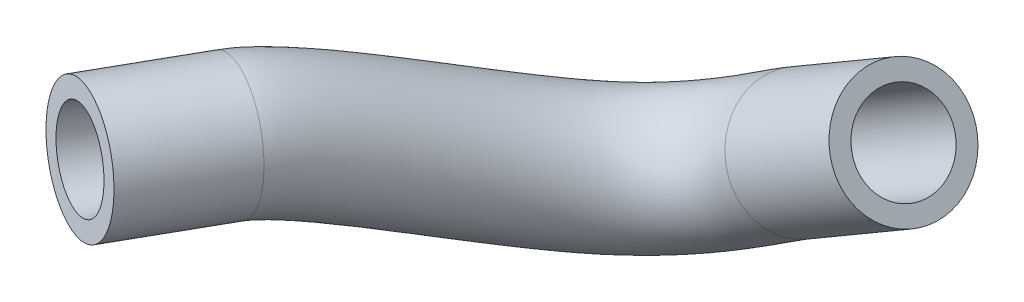
SolidWorks part; units mm, degrees
material "Silicon Rubber"
ref_plane "X-Y Datum" through (0, 0, 0) normal (0, 0, 1) x (1, 0, 0)
ref_plane "X-Z Datum" through (0, 0, 0) normal (0, 1, 0) x (1, 0, 0)
ref_plane "Y-Z Datum" through (0, 0, 0) normal (1, 0, 0) x (0, 0, -1)
sketch3d "3DSketch1"
  line L0 (-8.4082, 71.6879, 109.9525) -> (1.2518, 69.4078, 86.572)
  line L1 (58.6408, 60.7321, 18.5097) -> (85.1939, 77.7553, 22.1439)
  line L2 (58.6408, 60.7321, 18.5097) -> (85.1939, 77.7553, 22.1439) construction
  line L3 (-8.4082, 71.6879, 109.9525) -> (0.0443, 69.6928, 89.4946) construction
  line L4 (1.2518, 69.4078, 86.572) -> (-8.4082, 71.6879, 109.9525) construction
  circle A0 centre (-8.4082, 71.6879, 109.9525) radius 9.525 construction
  circle A9 centre (0.0443, 69.6928, 89.4946) radius 9.525 construction
  circle A10 centre (-8.4082, 71.6879, 109.9525) radius 9.525 construction
  circle A11 centre (0.0443, 69.6928, 89.4946) radius 9.525 construction
  spline S0 degree 3 poles (1.2518, 69.4078, 86.572) (5.9528, 68.2982, 75.1939) (26.8372, 38.6737, 21.8434) (51.3378, 56.0501, 17.5101) (58.6408, 60.7321, 18.5097) knots 0 0 0 0 0.528449 1 1 1 1
  point P1 (12.5064, 52.9241, 0)
  point P3 (-4.7857, 70.8329, 101.1848)
  point P8 (29.0353, 50.1135, 32.4963)
  point P10 (3.6667, 68.8378, 80.7269)
  point P12 (-4.7857, 70.8329, 101.1848)
  point P15 (3.6667, 68.8378, 80.7269)
  dimension "D1" = 25.4
sweep "Sweep1" add path "3DSketch1" circular profile diameter 26.9875 parameters "D3"=26.9875
sweep "Cut-Sweep1" cut path "3DSketch1<2>" circular profile diameter 19.05 parameters "D3"=19.05
sketch3d "3DSketch1<2>" same geometry as "3DSketch1"
sketch3d "3DSketch2" [suppressed]
  circle A0 centre (15.1451, 20.3909, 0) radius 9.525 construction
  circle A1 centre (15.1451, 20.3909, 0) radius 9.525 construction
  circle A2 centre (58.6408, 60.7321, 18.5097) radius 9.525 construction
  circle A3 centre (58.6408, 60.7321, 18.5097) radius 9.525 construction
  point P2 (9.4657, 12.7443, 0)
  point P4 (9.4657, 12.7443, 0)
  point P7 (50.6749, 55.6251, 17.4194)
  point P9 (50.6749, 55.6251, 17.4194)
